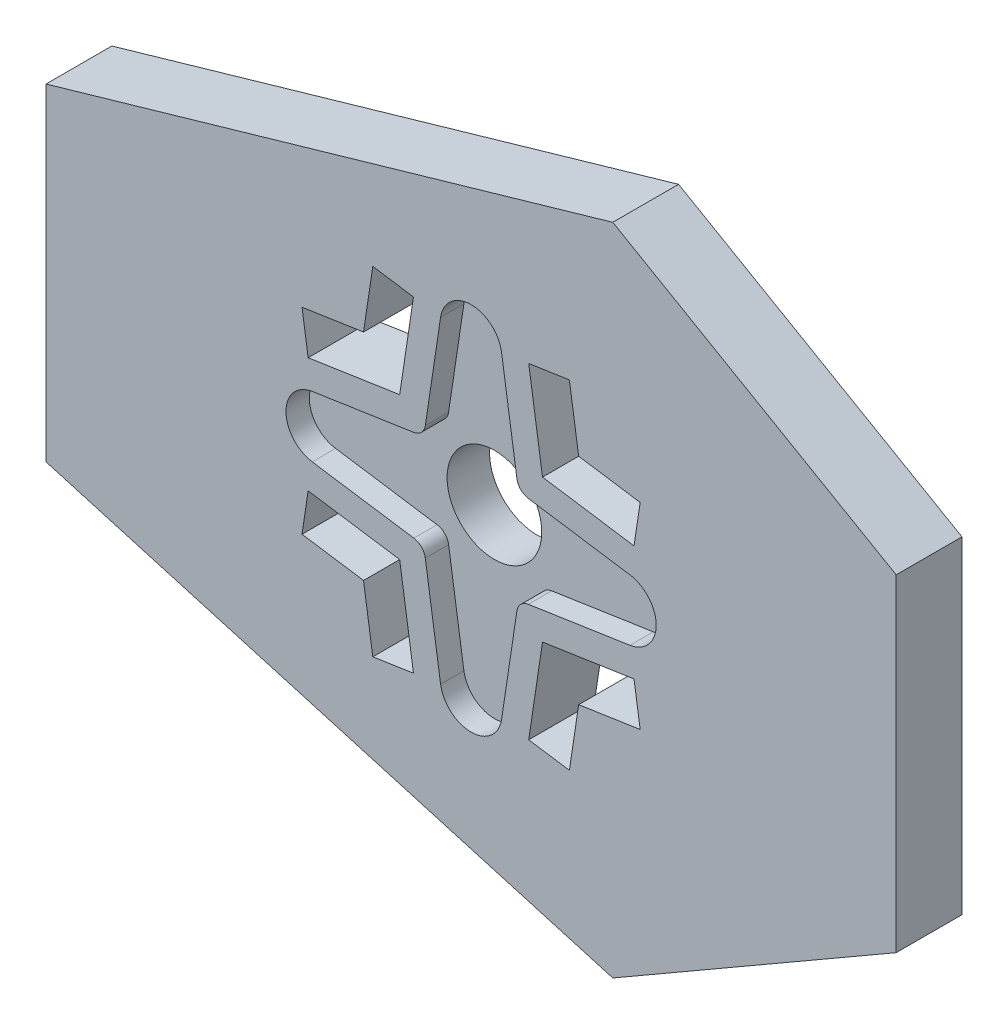
SolidWorks part; units mm, degrees
ref_plane "Front Plane" through (0, 0, 0) normal (0, 0, 1) x (1, 0, 0)
ref_plane "Top Plane" through (0, 0, 0) normal (0, 1, 0) x (1, 0, 0)
ref_plane "Right Plane" through (0, 0, 0) normal (1, 0, 0) x (0, 0, -1)
sketch "Sketch1" plane through (0, 0, 0) normal (0, 0, 1) x (1, 0, 0)
  line L0 (5.1833, -23.8638) -> (-36.15, -11.9319) construction
  line L1 (-36.15, 11.9319) -> (-36.15, -11.9319) construction
  line L2 (-36.15, 11.9319) -> (5.1833, 23.8638) construction
  line L3 (25.85, 11.9319) -> (5.1833, 23.8638) construction
  line L4 (25.85, -11.9319) -> (25.85, 11.9319) construction
  line L5 (5.1833, -23.8638) -> (25.85, -11.9319) construction
  line L6 (5.1833, -23.8638) -> (-36.15, -11.9319)
  line L7 (-36.15, 11.9319) -> (-36.15, -11.9319)
  line L8 (-36.15, 11.9319) -> (5.1833, 23.8638)
  line L9 (25.85, 11.9319) -> (5.1833, 23.8638)
  line L10 (25.85, -11.9319) -> (25.85, 11.9319)
  line L11 (5.1833, -23.8638) -> (25.85, -11.9319)
  line L20 (-2.9251, -11.5851) -> (-1.8099, -4.18)
  line L21 (-0.97, -3.3401) -> (6.4351, -2.2249)
  line L22 (6.4351, 2.2249) -> (-0.97, 3.3401)
  line L23 (-1.8099, 4.18) -> (-2.9251, 11.5851)
  line L24 (-7.3749, 11.5851) -> (-8.4901, 4.18)
  line L25 (-9.33, 3.3401) -> (-16.7351, 2.2249)
  line L26 (-16.7351, -2.2249) -> (-9.33, -3.3401)
  line L27 (-8.4901, -4.18) -> (-7.3749, -11.5851)
  line L28 (-2.9251, -11.5851) -> (-1.8099, -4.18)
  line L29 (-0.97, -3.3401) -> (6.4351, -2.2249)
  line L30 (6.4351, 2.2249) -> (-0.97, 3.3401)
  line L31 (-1.8099, 4.18) -> (-2.9251, 11.5851)
  line L32 (-7.3749, 11.5851) -> (-8.4901, 4.18)
  line L33 (-9.33, 3.3401) -> (-16.7351, 2.2249)
  line L34 (-16.7351, -2.2249) -> (-9.33, -3.3401)
  line L35 (-8.4901, -4.18) -> (-7.3749, -11.5851)
  circle A0 centre (-5.15, 0) radius 3.45 construction
  circle A1 centre (-5.15, 0) radius 3.45
  arc A8 (-0.97, -3.3401) -> (-1.8099, -4.18) centre (-0.8211, -4.3289) ccw
  arc A9 (6.4351, -2.2249) -> (6.4351, 2.2249) centre (6.1, 0) ccw
  arc A10 (-1.8099, 4.18) -> (-0.97, 3.3401) centre (-0.8211, 4.3289) ccw
  arc A11 (-2.9251, 11.5851) -> (-7.3749, 11.5851) centre (-5.15, 11.25) ccw
  arc A12 (-9.33, 3.3401) -> (-8.4901, 4.18) centre (-9.4789, 4.3289) ccw
  arc A13 (-16.7351, 2.2249) -> (-16.7351, -2.2249) centre (-16.4, 0) ccw
  arc A14 (-8.4901, -4.18) -> (-9.33, -3.3401) centre (-9.4789, -4.3289) ccw
  arc A15 (-7.3749, -11.5851) -> (-2.9251, -11.5851) centre (-5.15, -11.25) ccw
  arc A16 (-0.97, -3.3401) -> (-1.8099, -4.18) centre (-0.8211, -4.3289) ccw
  arc A17 (6.4351, -2.2249) -> (6.4351, 2.2249) centre (6.1, 0) ccw
  arc A18 (-1.8099, 4.18) -> (-0.97, 3.3401) centre (-0.8211, 4.3289) ccw
  arc A19 (-2.9251, 11.5851) -> (-7.3749, 11.5851) centre (-5.15, 11.25) ccw
  arc A20 (-9.33, 3.3401) -> (-8.4901, 4.18) centre (-9.4789, 4.3289) ccw
  arc A21 (-16.7351, 2.2249) -> (-16.7351, -2.2249) centre (-16.4, 0) ccw
  arc A22 (-8.4901, -4.18) -> (-9.33, -3.3401) centre (-9.4789, -4.3289) ccw
  arc A23 (-7.3749, -11.5851) -> (-2.9251, -11.5851) centre (-5.15, -11.25) ccw
  dimension "D1" = 0
extrude "Boss-Extrude1" add sketch "Sketch1" along normal up to surface (3.1 mm away) contours L8 L9 L10 L11 L6 L7 | A1
extrude "Boss-Extrude2" add sketch "Sketch1<3>" along normal up to surface (4.8 mm away) contours L6 L11 L10 L9 L8 L7 A23 L35 A22 L34 A21 L33 A20 L32 A19 L31 A18 L30 A17 L29 A16 L28 region at (-15.2663, -17.1461, 0)
sketch "Sketch1<3>" plane through (0, 0, 0) normal (0, 0, 1) x (1, 0, 0) same geometry as "Sketch1"
sketch "Sketch3" plane through (0, 0, 4.8) normal (0, 0, 1) x (1, 0, 0)
  line L0 (-12.9946, 7.8446) -> (-17.4796, 7.1692) construction
  line L1 (-17.4796, 7.1692) -> (-17.0329, 4.2026) construction
  line L2 (-10.3578, 5.2078) -> (-17.0329, 4.2026) construction
  line L3 (-9.3526, 11.8829) -> (-10.3578, 5.2078) construction
  line L4 (-12.3192, 12.3296) -> (-9.3526, 11.8829) construction
  line L5 (-12.3192, 12.3296) -> (-12.9946, 7.8446) construction
  line L6 (-12.9946, 7.8446) -> (-17.4796, 7.1692)
  line L7 (-17.4796, 7.1692) -> (-17.0329, 4.2026)
  line L8 (-10.3578, 5.2078) -> (-17.0329, 4.2026)
  line L9 (-9.3526, 11.8829) -> (-10.3578, 5.2078)
  line L10 (-12.3192, 12.3296) -> (-9.3526, 11.8829)
  line L11 (-12.3192, 12.3296) -> (-12.9946, 7.8446)
extrude "Cut-Extrude1" cut sketch "Sketch3" against normal through all
sketch "Sketch4" plane through (0, 0, 4.8) normal (0, 0, 1) x (1, 0, 0)
  line L0 (-5.15, 13.5) -> (-5.15, -13.5) construction
  line L1 (-18.65, 0) -> (8.35, 0) construction
  arc A0 (-2.9251, 11.5851) -> (-7.3749, 11.5851) centre (-5.15, 11.25) ccw construction
  arc A1 (-7.3749, -11.5851) -> (-2.9251, -11.5851) centre (-5.15, -11.25) ccw construction
  arc A2 (-16.7351, 2.2249) -> (-16.7351, -2.2249) centre (-16.4, 0) ccw construction
  arc A3 (6.4351, -2.2249) -> (6.4351, 2.2249) centre (6.1, 0) ccw construction
ref_plane "Plane1" through (-5.15, 0, 0) normal (-1, 0, 0) x (0, -1, 0)
ref_plane "Plane2" through (0, 0, 0) normal (0, -1, 0) x (1, 0, 0)
mirror "Mirror1" about plane through (-5.15, 0, 0) normal (-1, 0, 0) of "Cut-Extrude1"
mirror "Mirror2" about plane through (0, 0, 0) normal (0, -1, 0) of "Cut-Extrude1", "Mirror1"
